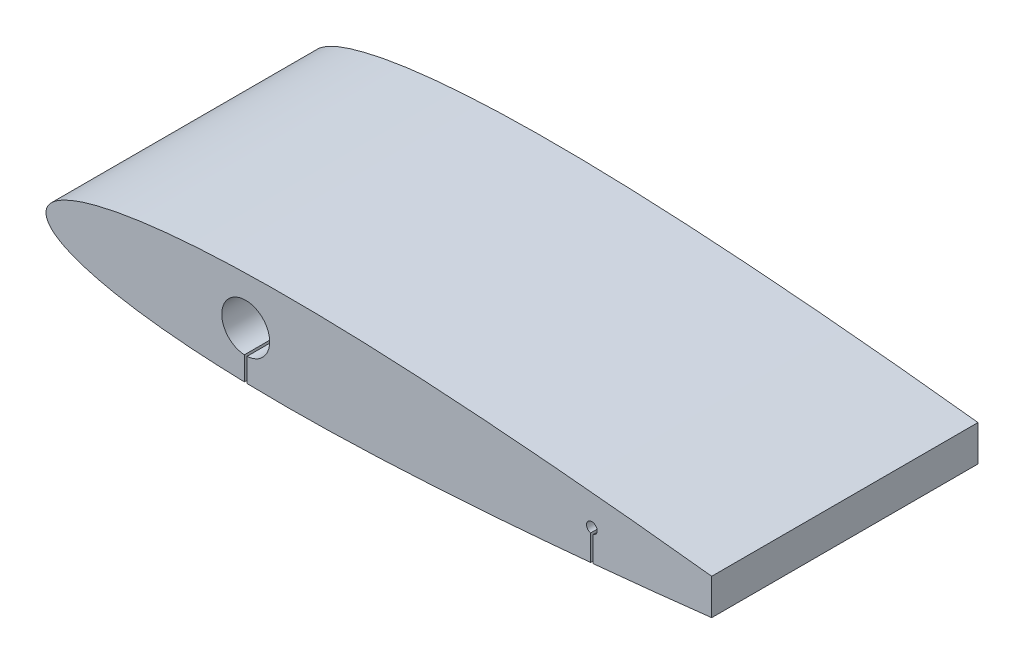
SolidWorks part; units mm, degrees
material "UoS Blue Foam"
ref_plane "Front Plane" through (0, 0, 0) normal (0, 0, 1) x (1, 0, 0)
ref_plane "Top Plane" through (0, 0, 0) normal (0, 1, 0) x (1, 0, 0)
ref_plane "Right Plane" through (0, 0, 0) normal (1, 0, 0) x (0, 0, -1)
sketch "Sketch5" plane through (0, 0, 0) normal (0, 0, 1) x (1, 0, 0)
  line L1 (300, 0.378) -> (300, -0.378)
  spline S1 degree 3 poles (300, 0.378) (299.2704, 0.4794) (297.2347, 0.7625) (293.6597, 1.2577) (289.1124, 1.8742) (284.0808, 2.5445) (278.752, 3.2381) (273.2659, 3.9349) (267.706, 4.629) (262.1146, 5.3131) (256.5083, 5.9822) (250.8917, 6.638) (245.2696, 7.2818) (239.6473, 7.9122) (234.0251, 8.527) (228.3991, 9.1262) (222.7683, 9.7131) (217.1359, 10.2875) (211.5054, 10.8469) (205.8776, 11.3916) (200.2515, 11.9209) (194.6264, 12.4346) (189.0028, 12.9319) (183.3815, 13.4131) (177.7632, 13.8764) (172.1483, 14.3212) (166.5375, 14.7478) (160.9317, 15.1542) (155.3317, 15.5391) (149.7375, 15.9026) (144.1487, 16.2418) (138.5657, 16.5574) (132.9909, 16.8474) (127.4274, 17.1102) (121.8776, 17.3439) (116.3408, 17.5453) (110.8155, 17.7127) (105.3013, 17.8445) (99.8006, 17.9401) (94.3174, 17.9966) (88.8558, 18.0101) (83.4186, 17.9792) (78.0085, 17.8992) (72.6285, 17.767) (67.2827, 17.5794) (61.9774, 17.3315) (56.7207, 17.021) (51.5252, 16.641) (46.4082, 16.1902) (41.3942, 15.6617) (36.5157, 15.054) (31.819, 14.3656) (27.3662, 13.6035) (23.2352, 12.7826) (19.5026, 11.9203) (16.2183, 11.0446) (13.3892, 10.1751) (10.9849, 9.3335) (8.9616, 8.5221) (7.2673, 7.747) (5.8461, 7.0106) (4.6477, 6.3006) (3.6282, 5.6065) (2.7519, 4.9266) (2.0063, 4.2499) (1.3906, 3.5703) (0.901, 2.8909) (0.5293, 2.2202) (0.2605, 1.5665) (0.0857, 0.931) (-0.0035, 0.309) (-0.0035, -0.309) (0.0857, -0.931) (0.2605, -1.5665) (0.5293, -2.2202) (0.901, -2.8909) (1.3906, -3.5703) (2.0063, -4.2499) (2.7519, -4.9266) (3.6282, -5.6065) (4.6477, -6.3006) (5.8461, -7.0106) (7.2673, -7.747) (8.9616, -8.5221) (10.9849, -9.3335) (13.3892, -10.1751) (16.2183, -11.0446) (19.5026, -11.9203) (23.2352, -12.7826) (27.3661, -13.6036) (31.8191, -14.3651) (36.5156, -15.0541) (41.3942, -15.6616) (46.4082, -16.1902) (51.5252, -16.641) (56.7207, -17.021) (61.9774, -17.3315) (67.2827, -17.5794) (72.6285, -17.767) (78.0085, -17.8992) (83.4186, -17.9792) (88.8558, -18.0101) (94.3174, -17.9966) (99.8006, -17.9401) (105.3013, -17.8445) (110.8155, -17.7127) (116.3408, -17.5453) (121.8776, -17.3439) (127.4274, -17.1102) (132.9909, -16.8474) (138.5657, -16.5574) (144.1487, -16.2418) (149.7375, -15.9026) (155.3317, -15.5391) (160.9317, -15.1542) (166.5375, -14.7478) (172.1483, -14.3212) (177.7632, -13.8764) (183.3815, -13.4131) (189.0028, -12.9319) (194.6264, -12.4346) (200.2515, -11.9209) (205.8776, -11.3916) (211.5054, -10.8469) (217.1359, -10.2875) (222.7683, -9.7131) (228.3991, -9.1262) (234.0251, -8.527) (239.6473, -7.9122) (245.2696, -7.2818) (250.8917, -6.638) (256.5083, -5.9822) (262.1146, -5.3131) (267.706, -4.629) (273.2659, -3.9349) (278.752, -3.2381) (284.0808, -2.5445) (289.1124, -1.8742) (293.6597, -1.2577) (297.2347, -0.7625) (299.2704, -0.4794) (300, -0.378) knots 0 0 0 0 0.003612 0.010079 0.017699 0.026115 0.034971 0.04405 0.053234 0.062448 0.071674 0.080921 0.090178 0.099424 0.108664 0.117912 0.12717 0.136427 0.145675 0.154916 0.164153 0.173387 0.182616 0.191838 0.201053 0.21026 0.219459 0.228647 0.237822 0.246985 0.256137 0.265279 0.274407 0.283512 0.292592 0.301646 0.310682 0.319699 0.328695 0.33766 0.346589 0.355477 0.364323 0.373122 0.381868 0.390553 0.399166 0.40769 0.416098 0.424355 0.432412 0.440205 0.447631 0.454564 0.460855 0.466413 0.471229 0.475366 0.478901 0.481915 0.484499 0.486747 0.488741 0.490543 0.492182 0.493673 0.495032 0.496279 0.497425 0.49849 0.499503 0.500497 0.50151 0.502575 0.503721 0.504968 0.506327 0.507818 0.509457 0.511259 0.513253 0.515501 0.518085 0.521099 0.524634 0.528771 0.533587 0.539145 0.545436 0.55237 0.559795 0.567588 0.575645 0.583902 0.59231 0.600834 0.609447 0.618132 0.626878 0.635677 0.644523 0.653411 0.66234 0.671305 0.680301 0.689318 0.698354 0.707408 0.716488 0.725593 0.734721 0.743863 0.753015 0.762178 0.771353 0.780541 0.78974 0.798947 0.808162 0.817384 0.826613 0.835847 0.845084 0.854325 0.863573 0.87283 0.882088 0.891336 0.900576 0.909822 0.919079 0.928326 0.937552 0.946766 0.95595 0.965029 0.973885 0.982301 0.989921 0.996388 1 1 1 1
  dimension "Tail chord" = 300
extrude "Boss-Extrude1" add sketch "Sketch5" along normal blind 100
ref_plane "Plane1" through (0, 0, 110) normal (0, 0, 1) x (1, 0, 0)
sketch "Sketch7" plane through (0, 0, 110) normal (0, 0, 1) x (1, 0, 0)
  circle A0 centre (75, 0) radius 9
  circle A1 centre (205, 0) radius 2
  dimension "D1" = 18
  dimension "D3" = 4
  dimension "Tail chord qtr" = 75
  dimension "Small hole" = 130
extrude "Cut-Extrude7" cut sketch "Sketch7" against normal through all
curve "Curve6"
  spline degree 3 poles (298.242, -0.1932, 0) (300.4407, 0, 0) (298.242, 0.1932, 0) (296.4349, 0.5367, 0) (292.0253, 1.0976, 0) (286.5771, 1.8592, 0) (279.4156, 2.8001, 0) (270.9173, 3.8949, 0) (261.066, 5.1159, 0) (250.0071, 6.4339, 0) (237.8495, 7.8187, 0) (224.7304, 9.2395, 0) (210.7923, 10.6647, 0) (196.1883, 12.0613, 0) (181.0783, 13.3946, 0) (165.6277, 14.6278, 0) (150.0058, 15.7225, 0) (134.3834, 16.6392, 0) (118.9317, 17.3387, 0) (103.8195, 17.7845, 0) (89.2123, 17.9443, 0) (75.2698, 17.7935, 0) (62.1444, 17.3161, 0) (49.9793, 16.5075, 0) (38.907, 15.374, 0) (29.0471, 13.9333, 0) (20.5034, 12.2128, 0) (13.3641, 10.246, 0) (7.6828, 8.0707, 0) (3.4992, 5.7028, 0) (0.7348, 3.1014, 0) (-0.3264, 0, 0) (0.7348, -3.1014, 0) (3.4992, -5.7028, 0) (7.6828, -8.0707, 0) (13.3641, -10.246, 0) (20.5034, -12.2128, 0) (29.0471, -13.9333, 0) (38.907, -15.374, 0) (49.9793, -16.5075, 0) (62.1444, -17.3161, 0) (75.2698, -17.7935, 0) (89.2123, -17.9443, 0) (103.8195, -17.7845, 0) (118.9317, -17.3387, 0) (134.3834, -16.6392, 0) (150.0058, -15.7225, 0) (165.6277, -14.6278, 0) (181.0783, -13.3946, 0) (196.1883, -12.0613, 0) (210.7923, -10.6647, 0) (224.7304, -9.2395, 0) (237.8495, -7.8187, 0) (250.0071, -6.4339, 0) (261.066, -5.1159, 0) (270.9173, -3.8949, 0) (279.4156, -2.8001, 0) (286.5771, -1.8592, 0) (292.0253, -1.0976, 0) (296.4349, -0.5367, 0) (298.242, -0.1932, 0) (300.4407, 0, 0) (298.242, 0.1932, 0) knots -0.012119 -0.005412 -0.001357 0 0.001357 0.005412 0.012119 0.021403 0.033159 0.047255 0.063534 0.081814 0.101892 0.123547 0.146538 0.170613 0.195504 0.220938 0.246636 0.272314 0.297694 0.3225 0.346466 0.36934 0.390884 0.410879 0.429129 0.445462 0.459736 0.471848 0.481751 0.489494 0.495334 0.5 0.504666 0.510506 0.518249 0.528152 0.540264 0.554538 0.570871 0.589121 0.609116 0.63066 0.653534 0.6775 0.702306 0.727686 0.753364 0.779062 0.804496 0.829387 0.853462 0.876453 0.898108 0.918186 0.936466 0.952745 0.966841 0.978597 0.987881 0.994588 0.998643 1 1.001357 1.005412 1.012119 periodic
sketch "Sketch8" plane through (0, 0, 0) normal (0, 0, 1) x (1, 0, 0)
  spline S0 degree 3 poles (298.242, -0.1932) (300.4407, 0) (298.242, 0.1932) (296.4349, 0.5367) (292.0253, 1.0976) (286.5771, 1.8592) (279.4156, 2.8001) (270.9173, 3.8949) (261.066, 5.1159) (250.0071, 6.4339) (237.8495, 7.8187) (224.7304, 9.2395) (210.7923, 10.6647) (196.1883, 12.0613) (181.0783, 13.3946) (165.6277, 14.6278) (150.0058, 15.7225) (134.3834, 16.6392) (118.9317, 17.3387) (103.8195, 17.7845) (89.2123, 17.9443) (75.2698, 17.7935) (62.1444, 17.3161) (49.9793, 16.5075) (38.907, 15.374) (29.0471, 13.9333) (20.5034, 12.2128) (13.3641, 10.246) (7.6828, 8.0707) (3.4992, 5.7028) (0.7348, 3.1014) (-0.3264, 0) (0.7348, -3.1014) (3.4992, -5.7028) (7.6828, -8.0707) (13.3641, -10.246) (20.5034, -12.2128) (29.0471, -13.9333) (38.907, -15.374) (49.9793, -16.5075) (62.1444, -17.3161) (75.2698, -17.7935) (89.2123, -17.9443) (103.8195, -17.7845) (118.9317, -17.3387) (134.3834, -16.6392) (150.0058, -15.7225) (165.6277, -14.6278) (181.0783, -13.3946) (196.1883, -12.0613) (210.7923, -10.6647) (224.7304, -9.2395) (237.8495, -7.8187) (250.0071, -6.4339) (261.066, -5.1159) (270.9173, -3.8949) (279.4156, -2.8001) (286.5771, -1.8592) (292.0253, -1.0976) (296.4349, -0.5367) (298.242, -0.1932) (300.4407, 0) (298.242, 0.1932) knots -0.012119 -0.005412 -0.001357 0 0.001357 0.005412 0.012119 0.021403 0.033159 0.047255 0.063534 0.081814 0.101892 0.123547 0.146538 0.170613 0.195504 0.220938 0.246636 0.272314 0.297694 0.3225 0.346466 0.36934 0.390884 0.410879 0.429129 0.445462 0.459736 0.471848 0.481751 0.489494 0.495334 0.5 0.504666 0.510506 0.518249 0.528152 0.540264 0.554538 0.570871 0.589121 0.609116 0.63066 0.653534 0.6775 0.702306 0.727686 0.753364 0.779062 0.804496 0.829387 0.853462 0.876453 0.898108 0.918186 0.936466 0.952745 0.966841 0.978597 0.987881 0.994588 0.998643 1 1.001357 1.005412 1.012119 only from (300, 0) to (300, 0) construction
  spline S1 degree 3 poles (298.242, -0.1932) (300.4407, 0) (298.242, 0.1932) (296.4349, 0.5367) (292.0253, 1.0976) (286.5771, 1.8592) (279.4156, 2.8001) (270.9173, 3.8949) (261.066, 5.1159) (250.0071, 6.4339) (237.8495, 7.8187) (224.7304, 9.2395) (210.7923, 10.6647) (196.1883, 12.0613) (181.0783, 13.3946) (165.6277, 14.6278) (150.0058, 15.7225) (134.3834, 16.6392) (118.9317, 17.3387) (103.8195, 17.7845) (89.2123, 17.9443) (75.2698, 17.7935) (62.1444, 17.3161) (49.9793, 16.5075) (38.907, 15.374) (29.0471, 13.9333) (20.5034, 12.2128) (13.3641, 10.246) (7.6828, 8.0707) (3.4992, 5.7028) (0.7348, 3.1014) (-0.3264, 0) (0.7348, -3.1014) (3.4992, -5.7028) (7.6828, -8.0707) (13.3641, -10.246) (20.5034, -12.2128) (29.0471, -13.9333) (38.907, -15.374) (49.9793, -16.5075) (62.1444, -17.3161) (75.2698, -17.7935) (89.2123, -17.9443) (103.8195, -17.7845) (118.9317, -17.3387) (134.3834, -16.6392) (150.0058, -15.7225) (165.6277, -14.6278) (181.0783, -13.3946) (196.1883, -12.0613) (210.7923, -10.6647) (224.7304, -9.2395) (237.8495, -7.8187) (250.0071, -6.4339) (261.066, -5.1159) (270.9173, -3.8949) (279.4156, -2.8001) (286.5771, -1.8592) (292.0253, -1.0976) (296.4349, -0.5367) (298.242, -0.1932) (300.4407, 0) (298.242, 0.1932) knots -0.012119 -0.005412 -0.001357 0 0.001357 0.005412 0.012119 0.021403 0.033159 0.047255 0.063534 0.081814 0.101892 0.123547 0.146538 0.170613 0.195504 0.220938 0.246636 0.272314 0.297694 0.3225 0.346466 0.36934 0.390884 0.410879 0.429129 0.445462 0.459736 0.471848 0.481751 0.489494 0.495334 0.5 0.504666 0.510506 0.518249 0.528152 0.540264 0.554538 0.570871 0.589121 0.609116 0.63066 0.653534 0.6775 0.702306 0.727686 0.753364 0.779062 0.804496 0.829387 0.853462 0.876453 0.898108 0.918186 0.936466 0.952745 0.966841 0.978597 0.987881 0.994588 0.998643 1 1.001357 1.005412 1.012119 only from (300, 0) to (300, 0)
sketch "Sketch9" plane through (0, 0, 0) normal (0, 1, 0) x (1, 0, 0)
  line L0 (0.0001, -100) -> (300, -100) construction
  line L1 (300, 0) -> (250, 0)
  line L2 (300, 0) -> (300, -100)
  line L3 (300, -100) -> (250, -100)
  line L4 (250, 0) -> (250, -100)
  dimension "Rudder" = 50
extrude "Cut-Extrude8" cut sketch "Sketch9" against normal blind 20 and the other way blind 20
sketch "Sketch10" plane through (0, 0, 0) normal (0, 1, 0) x (1, 0, 0)
  line L0 (0, 0) -> (300, 0) construction
  line L1 (74.5001, 0) -> (75.5001, 0)
  line L2 (74.5001, 0) -> (74.5001, -100)
  line L3 (74.5001, -100) -> (75.5001, -100)
  line L4 (75.5001, 0) -> (75.5001, -100)
  line L5 (0.0001, -100) -> (250, -100) construction
  line L6 (0.0001, 0) -> (0.0001, -100) construction
  line L8 (204.5001, 0) -> (205.5001, 0)
  line L9 (204.5001, 0) -> (204.5001, -100)
  line L10 (204.5001, -100) -> (205.5001, -100)
  line L11 (205.5001, 0) -> (205.5001, -100)
  dimension "D1" = 1
  dimension "Box cut" = 74.5
  dimension "D2" = 1
  dimension "Small hole box cut distance" = 130
extrude "Cut-Extrude9" cut sketch "Sketch10" against normal blind 20
sketch "Sketch11" plane through (0, 0, 0) normal (0, 1, 0) x (1, 0, 0)
  line L0 (300, 0) -> (0, 0) construction
  line L1 (152.92, -67.315) -> (197.08, -67.315)
  line L2 (152.92, -67.315) -> (152.92, -32.685)
  line L3 (152.92, -32.685) -> (197.08, -32.685)
  line L4 (197.08, -67.315) -> (197.08, -32.685)
  dimension "Slot length" = 44.16
  dimension "Width servo slot" = 34.63
  dimension "Slot dist" = 32.685
  dimension "Slot post" = 152.92
extrude "Cut-Extrude10" cut sketch "Sketch11" against normal through all
equation "\"Tail chord qtr@Sketch7\" = \"Tail chord@Sketch5\" * 0.25"
equation "\"Small hole@Sketch7\" = \"Tail chord qtr@Sketch7\" * 2 - 20"
equation "\"Box cut@Sketch10\" = \"Tail chord qtr@Sketch7\" - 0.5"
equation "\"Slot dist@Sketch11\" = \"Width vert stab@Boss-Extrude1\" / 2 - \"Width servo slot@Sketch11\" / 2"
equation "\"Slot post@Sketch11\"=( \"Tail chord@Sketch5\" - \"Rudder@Sketch9\" )  / 2 - \"Slot length@Sketch11\" / 2+50"
equation "\"Chord\"= 300mm'Tail chord"
equation "\"Tail chord@Sketch5\"=\"Chord\""
equation "\"Small hole box cut distance@Sketch10\" = \"Tail chord qtr@Sketch7\" * 2 - 20"
